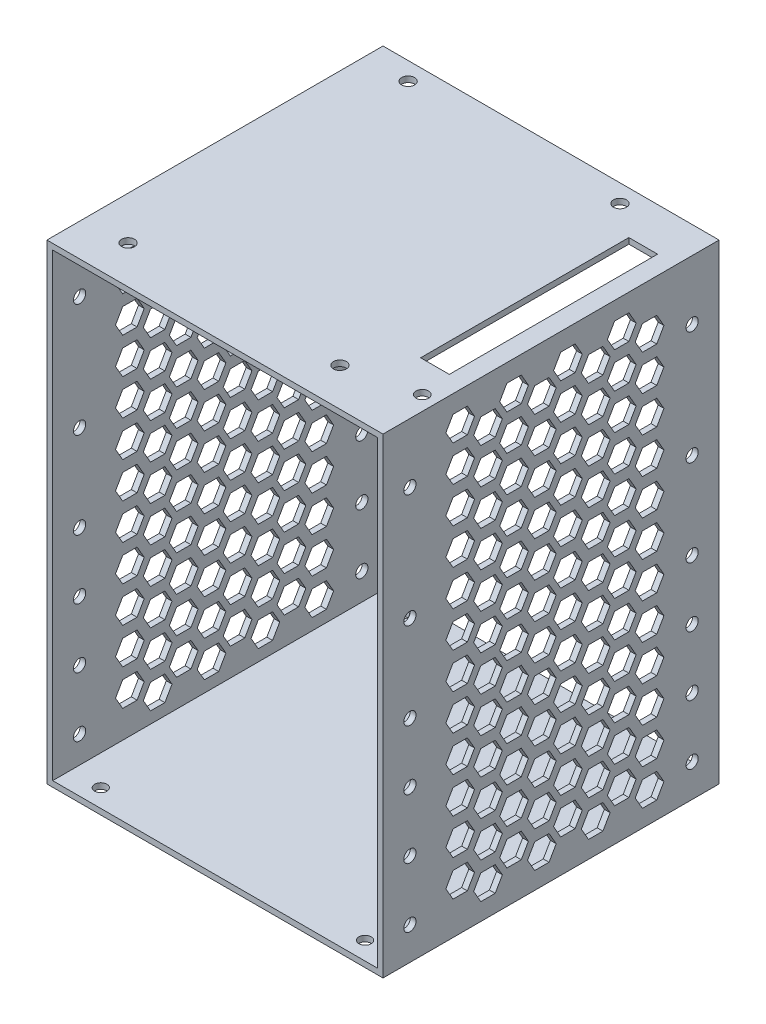
SolidWorks part; units mm, degrees
ref_plane "Front Plane" through (0, 0, 0) normal (0, 0, 1) x (1, 0, 0)
ref_plane "Top Plane" through (0, 0, 0) normal (0, 1, 0) x (1, 0, 0)
ref_plane "Right Plane" through (0, 0, 0) normal (1, 0, 0) x (0, 0, -1)
sketch "Sketch1" plane through (0, 0, 0) normal (0, 0, 1) x (1, 0, 0)
  line L0 (-45.2, 26.84) -> (45.2, 26.84)
  line L1 (45.2, 26.84) -> (45.2, -101.16)
  line L2 (45.2, -101.16) -> (-45.2, -101.16)
  line L3 (-45.2, -101.16) -> (-45.2, 26.84)
  line L5 (-46.8, 28.44) -> (46.8, 28.44)
  line L6 (-46.8, 28.44) -> (-46.8, -102.76)
  line L7 (-46.8, -102.76) -> (46.8, -102.76)
  line L8 (46.8, 28.44) -> (46.8, -102.76)
  dimension "D1" = 90.4
  dimension "D2" = 128
  dimension "D3" = 1.6
  dimension "D4" = 1.6
  dimension "D5" = 1.6
  dimension "D6" = 1.6
  dimension "D7" = 45.2
  dimension "D8" = 45.2
extrude "Boss-Extrude1" add sketch "Sketch1" along normal blind 93.6
sketch "Sketch2" plane through (46.8, 0, 0) normal (1, 0, 0) x (0, 0, -1)
  line L0 (-93.6, 28.44) -> (-93.6, -102.76)
  line L1 (-93.6, 28.44) -> (0, 28.44) construction
  line L2 (-93.6, -102.76) -> (-93.6, 28.44) construction
  line L3 (-93.6, -102.76) -> (0, -102.76) construction
  line L4 (-93.6, -85.36) -> (0, -85.36) construction
  line L5 (0, -102.76) -> (0, 28.44) construction
  line L6 (-93.6, -68.76) -> (0, -68.76) construction
  line L7 (-93.6, -52.16) -> (0, -52.16) construction
  line L8 (-93.6, -35.56) -> (0, -35.56) construction
  line L9 (-93.6, -3.96) -> (0, -3.96) construction
  line L10 (-93.6, -43.86) -> (0, -43.86)
  line L11 (-93.6, -60.46) -> (0, -60.46)
  line L12 (-93.6, -77.06) -> (0, -77.06)
  line L13 (-93.6, -93.66) -> (0, -93.66)
  line L14 (-93.6, -19.76) -> (0, -19.76)
  line L15 (-93.6, 11.84) -> (0, 11.84)
  line L16 (-93.6, -12.26) -> (0, -12.26)
  line L17 (-93.6, -84.56) -> (0, -84.56)
  line L18 (0, -84.56) -> (0, -86.16)
  line L19 (0, -86.16) -> (-93.6, -86.16)
  line L20 (-93.6, -67.96) -> (0, -67.96)
  line L21 (0, -67.96) -> (0, -69.56)
  line L22 (0, -69.56) -> (-93.6, -69.56)
  line L23 (-93.6, -51.36) -> (0, -51.36)
  line L24 (0, -51.36) -> (0, -52.96)
  line L25 (0, -52.96) -> (-93.6, -52.96)
  line L26 (-93.6, -34.76) -> (0, -34.76)
  line L27 (-93.6, -36.36) -> (0, -36.36)
  line L29 (-93.6, -3.16) -> (0, -3.16)
  line L30 (0, -3.16) -> (0, -4.76)
  line L31 (0, -4.76) -> (-93.6, -4.76)
  circle A11 centre (-86.1, 11.84) radius 0.75
  circle A13 centre (-86.1, -19.76) radius 0.75
  circle A14 centre (-86.1, -43.86) radius 0.75
  circle A15 centre (-86.1, -60.46) radius 0.75
  circle A16 centre (-86.1, -77.06) radius 0.75
  circle A17 centre (-86.1, -93.66) radius 0.75
  circle A18 centre (-7.5, 11.84) radius 0.75
  circle A20 centre (-7.5, -19.76) radius 0.75
  circle A21 centre (-7.5, -43.86) radius 0.75
  circle A22 centre (-7.5, -60.46) radius 0.75
  circle A23 centre (-7.5, -77.06) radius 0.75
  circle A24 centre (-7.5, -93.66) radius 0.75
  circle A25 centre (-84, -12.26) radius 0.75
  circle A26 centre (-10, -12.26) radius 0.75
  dimension "D7" = 16.6
  dimension "D8" = 15.8
  dimension "D9" = 8.3
  dimension "D10" = 8.3
  dimension "D11" = 8.3
  dimension "D12" = 8.3
  dimension "D13" = 1.5
  dimension "D14" = 7.5
  dimension "D15" = 7.5
  dimension "D16" = 1.5
  dimension "D17" = 1.5
  dimension "D18" = 1.5
  dimension "D19" = 1.5
  dimension "D20" = 1.5
  dimension "D21" = 1.5
  dimension "D22" = 1.5
  dimension "D23" = 1.5
  dimension "D24" = 1.5
  dimension "D25" = 1.5
  dimension "D26" = 1.5
  dimension "D1" = 17.4
  dimension "D2" = 16.6
  dimension "D3" = 16.6
  dimension "D4" = 16.6
  dimension "D5" = 31.6
  dimension "D6" = 32.4
  dimension "D27" = 8.3
  dimension "D28" = 0.8
  dimension "D29" = 0.8
  dimension "D30" = 0.8
  dimension "D31" = 0.8
  dimension "D32" = 0.8
  dimension "D33" = 0.8
  dimension "D34" = 0.8
  dimension "D35" = 0.8
  dimension "D36" = 0.8
  dimension "D37" = 0.8
  dimension "D38" = 15
extrude "Cut-Extrude1" cut sketch "Sketch2" against normal blind 100 contours L15 A11 | L15 A11 | L15 A18 | L15 A18 | L14 A13 | L14 A13 | L10 A21 | L10 A14 | L11 A15 | L11 A22 | L11 A22 | L12 A16 | L12 A16 | L12 A23 | L13 A17 | L13 A17 | L12 A23 | L13 A24 | L13 A24 | A20 | A21 | A14 | A15 region at (46.8, -19.4417, 86.1) region at (46.8, -20.0783, 86.1) region at (46.8, -44.1783, 7.5) region at (46.8, -43.5417, 86.1) region at (46.8, -60.1417, 7.5) region at (46.8, -60.7783, 7.5) region at (46.8, -60.1417, 86.1) region at (46.8, -76.7417, 7.5) region at (46.8, -77.3783, 7.5) region at (46.8, -76.7417, 86.1) region at (46.8, -77.3783, 86.1) region at (46.8, -93.3417, 7.5) region at (46.8, -93.9783, 7.5) region at (46.8, -93.3417, 86.1) region at (46.8, -93.9783, 86.1) region at (46.8, 12.1583, 7.5) region at (46.8, 11.5217, 7.5) region at (46.8, 12.1583, 86.1) region at (46.8, 11.5217, 86.1)
sketch "Sketch6" plane through (46.8, 0, 0) normal (1, 0, 0) x (0, 0, -1)
  line L0 (-76.1, 19.9759) -> (-74.1, 23.44)
  line L1 (-74.1, 23.44) -> (-70.1, 23.44)
  line L2 (-70.1, 23.44) -> (-68.1, 19.9759)
  line L3 (-68.1, 19.9759) -> (-70.1, 16.5118)
  line L4 (-70.1, 16.5118) -> (-74.1, 16.5118)
  line L5 (-74.1, 16.5118) -> (-76.1, 19.9759)
  line L18 (-93.6, 28.44) -> (0, 28.44) construction
  line L19 (-93.6, -102.76) -> (-93.6, 28.44) construction
  line L20 (-68.3557, 15.5047) -> (-66.3557, 18.9688)
  line L21 (-66.3557, 18.9688) -> (-62.3557, 18.9688)
  line L22 (-62.3557, 18.9688) -> (-60.3557, 15.5047)
  line L23 (-60.3557, 15.5047) -> (-62.3557, 12.0406)
  line L24 (-62.3557, 12.0406) -> (-66.3557, 12.0406)
  line L25 (-66.3557, 12.0406) -> (-68.3557, 15.5047)
  dimension "D1" = 120
  dimension "D2" = 120
  dimension "D3" = 120
  dimension "D4" = 4
  dimension "D5" = 4
  dimension "D6" = 4
  dimension "D7" = 4
  dimension "D8" = 5
  dimension "D9" = 17.5
  dimension "D10" = 120
  dimension "D11" = 120
  dimension "D12" = 120
  dimension "D13" = 4
  dimension "D14" = 4
  dimension "D15" = 4
  dimension "D16" = 4
  dimension "D17" = 2.0142
  dimension "D18" = 2.0142
  dimension "D19" = 25.2443
extrude "Cut-Extrude4" cut sketch "Sketch6" against normal blind 100
pattern_linear "LPattern2" count 4 spacing 15 along (0, 0, -1) count 12 spacing 10 along (0, -1, 0) of "Cut-Extrude4"
hole_wizard "M3 Clearance Hole1" positions "Sketch7" profile "Sketch8" hole size "M3" standard "ANSI Metric" end condition through all
sketch "Sketch7" plane through (-46.8, 0, 0) normal (-1, 0, 0) x (0, 0, 1)
  point P0 (7.5, 11.84)
  point P3 (86.1, 11.84)
  point P6 (7.5, -19.76)
  point P9 (7.5, -43.86)
  point P12 (86.1, -19.76)
  point P15 (86.1, -43.86)
  point P18 (86.1, -60.46)
  point P21 (86.1, -77.06)
  point P26 (7.5, -93.66)
  point P29 (7.5, -77.06)
  point P32 (7.5, -60.46)
  point P40 (86.1, -93.66)
sketch "Sketch8" plane through (-46.8, 11.84, 7.5) normal (0, 1, 0) x (0, 0, 1)
  line L0 (0, 0) -> (0, 93.6)
  line L1 (0, 93.6) -> (1.7, 93.6)
  line L2 (1.7, 93.6) -> (1.7, 0)
  line L5 (1.7, 0) -> (0, 0)
  line L11 (0, -6.35) -> (0, 107.95) construction
  dimension "Thru Hole Dia." = 3.4
  dimension "Thru Hole Depth" = 93.6
sketch "Sketch9" plane through (0, 0, 0) normal (0, 0, 1) x (1, 0, 0)
  line L1 (-30, -108.3026) -> (30, -108.3026)
  line L2 (-30, -108.3026) -> (-30, -39.5314)
  line L3 (-30, -39.5314) -> (30, -39.5314)
  line L4 (30, -108.3026) -> (30, -39.5314)
  dimension "D1" = 30
  dimension "D2" = 30
sketch "Sketch10" plane through (0, -102.76, 0) normal (0, -1, 0) x (1, 0, 0)
  line L0 (45.2, 93.6) -> (-45.2, 93.6) construction
  line L3 (-46.8, 0) -> (46.8, 0) construction
  line L5 (-46.8, 0) -> (46.8, 0) construction
  line L6 (-46.8, 93.6) -> (46.8, 93.6) construction
  line L7 (-46.8, 93.6) -> (-46.8, 0) construction
  line L8 (46.8, 93.6) -> (46.8, 0) construction
  circle A0 centre (-36.8, 88.6) radius 2.9453
  circle A1 centre (-36.8, 5) radius 1.9301
  circle A2 centre (36.8, 5) radius 1.9498
  circle A3 centre (36.8, 88.6) radius 2.427
  dimension "D1" = 5
  dimension "D2" = 10
  dimension "D3" = 10
  dimension "D4" = 5
  dimension "D5" = 10
  dimension "D6" = 5
  dimension "D7" = 5
  dimension "D8" = 10
hole_wizard "M3 Clearance Hole2" positions "Sketch11" profile "Sketch12" hole size "M3" standard "ANSI Metric" end condition up to next
sketch "Sketch11" plane through (0, -102.76, 0) normal (0, -1, 0) x (-1, 0, 0)
  point P0 (-36.8, -5)
  point P3 (-36.8, -88.6)
  point P6 (36.8, -88.6)
  point P9 (36.8, -5)
sketch "Sketch12" plane through (36.8, -102.76, 5) normal (1, 0, 0) x (0, 0, -1)
  line L0 (0, 0) -> (0, 1.6)
  line L1 (0, 1.6) -> (1.7, 1.6)
  line L2 (1.7, 1.6) -> (1.7, 0)
  line L5 (1.7, 0) -> (0, 0)
  line L11 (0, -6.35) -> (0, 107.95) construction
  dimension "Thru Hole Dia." = 3.4
  dimension "Thru Hole Depth" = 1.6
sketch "Sketch16" plane through (0, 28.44, 0) normal (0, 1, 0) x (1, 0, 0)
  line L0 (46.8, -93.6) -> (46.8, 0) construction
  line L1 (46.8, -93.6) -> (-46.8, -93.6) construction
  circle A0 centre (42.75, -78.6) radius 1.75
  dimension "D1" = 3.5
  dimension "D2" = 4.05
  dimension "D3" = 15
extrude "Cut-Extrude6" cut sketch "Sketch16" against normal blind 141
hole_wizard "M3 Clearance Hole3" positions "Sketch17" profile "Sketch18" hole size "M3" standard "ANSI Metric" end condition up to next
sketch "Sketch17" plane through (0, 28.44, 0) normal (0, 1, 0) x (1, 0, 0)
  line L0 (-46.8, -93.6) -> (-46.8, 0) construction
  line L2 (46.8, 0) -> (-46.8, 0) construction
  circle A0 centre (42.75, -78.6) radius 1.75 construction
  point P0 (-34.8, -5)
  point P2 (-34.8, -83)
  point P4 (24.2, -83)
  point P6 (24.2, -5)
  dimension "D1" = 12
  dimension "D2" = 5
  dimension "D3" = 59
  dimension "D4" = 78
  dimension "D5" = 18.55
sketch "Sketch18" plane through (-34.8, 28.44, 5) normal (1, 0, 0) x (0, 0, 1)
  line L0 (0, 0) -> (0, 1.6)
  line L1 (0, 1.6) -> (1.8, 1.6)
  line L2 (1.8, 1.6) -> (1.8, 0)
  line L5 (1.8, 0) -> (0, 0)
  line L11 (0, -6.35) -> (0, 107.95) construction
  dimension "Thru Hole Dia." = 3.6
  dimension "Thru Hole Depth" = 1.6
sketch "Sketch19" plane through (0, 28.44, 0) normal (0, 1, 0) x (1, 0, 0)
  line L1 (33.6396, -69.9694) -> (41.6396, -69.9694)
  line L2 (33.6396, -69.9694) -> (33.6396, -11.9694)
  line L3 (33.6396, -11.9694) -> (41.6396, -11.9694)
  line L4 (41.6396, -69.9694) -> (41.6396, -11.9694)
  dimension "D1" = 58
  dimension "D2" = 8
extrude "Cut-Extrude7" cut sketch "Sketch19" against normal blind 1.6
